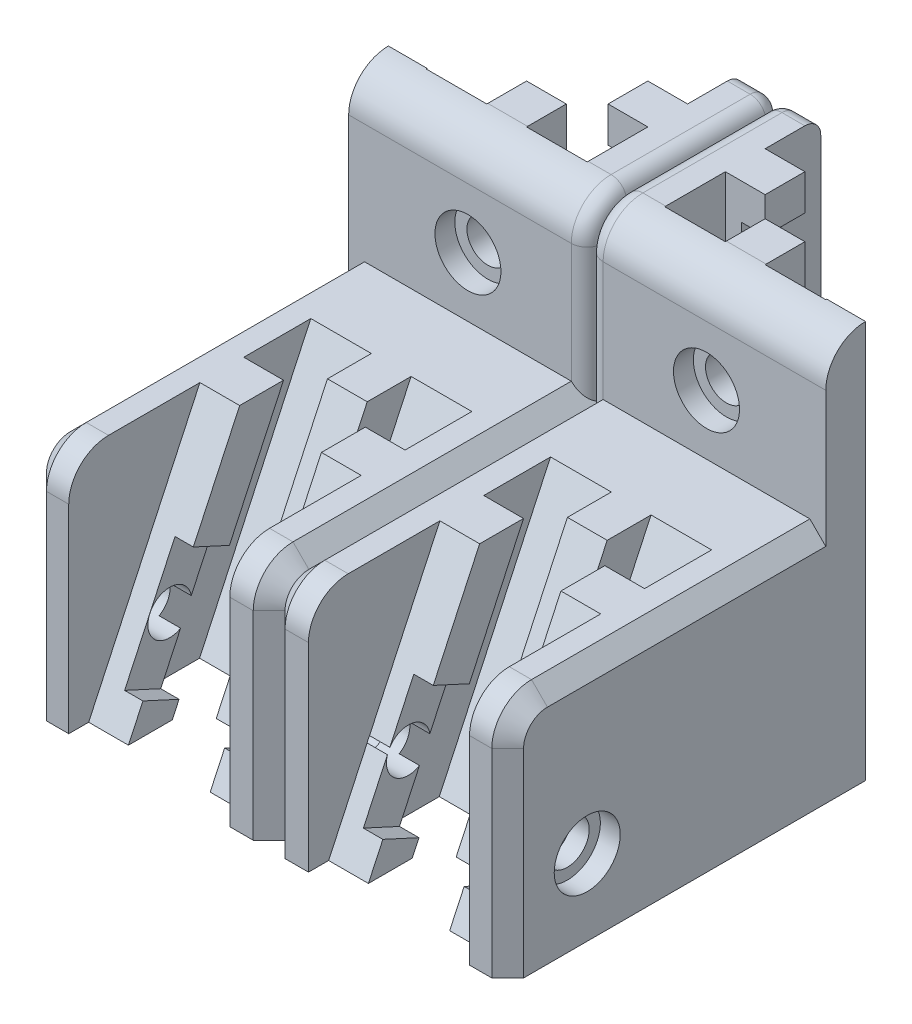
SolidWorks part; units mm, degrees
ref_plane "Front Plane" through (0, 0, 0) normal (0, 0, 1) x (1, 0, 0)
ref_plane "Top Plane" through (0, 0, 0) normal (0, 1, 0) x (1, 0, 0)
ref_plane "Right Plane" through (0, 0, 0) normal (1, 0, 0) x (0, 0, -1)
sketch "Z extrusion mount" plane through (0, 0, 0) normal (0, 1, 0) x (1, 0, 0)
  line L1 (-15, -15) -> (15, -15)
  line L2 (-15, -15) -> (-15, 15)
  line L3 (-15, 15) -> (15, 15)
  line L4 (15, -15) -> (15, 15)
  line L5 (-15, -15) -> (15, 15) construction
  line L6 (-15, 15) -> (15, -15) construction
  point P0 (0, 0)
  dimension "D1" = 30
  dimension "D2" = 30
extrude "Boss-Extrude1" add sketch "Z extrusion mount" along normal blind 50
sketch "Sketch2" plane through (0, 50, 0) normal (0, 1, 0) x (1, 0, 0)
  line L0 (0, 10.125) -> (0, -10.125) construction
  line L1 (-10.125, -10.125) -> (10.125, -10.125)
  line L2 (-10.125, -10.125) -> (-10.125, 10.125)
  line L3 (-10.125, 10.125) -> (10.125, 10.125)
  line L4 (10.125, -10.125) -> (10.125, 10.125)
  line L5 (-10.125, -10.125) -> (10.125, 10.125) construction
  line L6 (-10.125, 10.125) -> (10.125, -10.125) construction
  line L7 (-10.125, 0) -> (10.125, 0) construction
  line L8 (0, -10.125) -> (-2.5, -10.125)
  line L9 (-2.5, -10.125) -> (-2.5, -5.125)
  line L10 (-2.5, -5.125) -> (2.5, -5.125)
  line L11 (2.5, -5.125) -> (2.5, -10.125)
  line L12 (10.125, 2.5) -> (5.125, 2.5)
  line L13 (5.125, 2.5) -> (5.125, -2.5)
  line L14 (5.125, -2.5) -> (10.125, -2.5)
  point P0 (0, 0)
  dimension "D1" = 20.25
  dimension "D2" = 20.25
  dimension "D3" = 5
  dimension "D4" = 5
  dimension "D5" = 2.5
  dimension "D6" = 2.5
  dimension "D7" = 5
  dimension "D8" = 5
extrude "Cut-Extrude1" cut sketch "Sketch2" against normal blind 50 contours L10 L11 L1 L4 L3 L2 L9 region at (-0.5294, 50, -0.5294)
sketch "Sketch3" plane through (0, 50, 0) normal (0, 1, 0) x (1, 0, 0)
  line L0 (15, -15) -> (15, 15) construction
  line L1 (-15, 15) -> (15, 15)
  line L2 (-15, 15) -> (-15, 9.4943)
  line L3 (-15, 9.4943) -> (15, 9.4943)
  line L4 (15, 15) -> (15, 9.4943)
extrude "Cut-Extrude3" cut sketch "Sketch3" against normal blind 50
sketch "Sketch4" plane through (0, 0, 15) normal (0, 0, 1) x (1, 0, 0)
  line L0 (15, 50) -> (15, 0) construction
  line L1 (-15, 0) -> (15, 0)
  line L2 (-15, 0) -> (-15, 30)
  line L3 (-15, 30) -> (15, 30)
  line L4 (15, 0) -> (15, 30)
  line L5 (-15, 0) -> (15, 30) construction
  line L6 (-15, 30) -> (15, 0) construction
  point P0 (0, 15)
  dimension "D1" = 30
extrude "Boss-Extrude3" add sketch "Sketch4" along normal blind 40
sketch "Sketch11" plane through (-15, 0, 0) normal (-1, 0, 0) x (0, 0, 1)
  line L0 (35, 30) -> (55, -12.8901) construction
  line L1 (55, 30) -> (15, 30) construction
  line L2 (55, 30) -> (55, 0) construction
  line L3 (45, 8.5549) -> (45, 9.5549) construction
  circle A0 centre (45, 9.5549) radius 2.75
  dimension "D2" = 5.5
  dimension "D1" = 65
  dimension "D3" = 1
ref_plane "45 Angle Plane" through (-15, 30, 35) normal (0, 0.9063, -0.4226) x (-1, 0, 0)
sketch "Sketch12" plane through (-15, 30, 35) normal (0, 0.9063, -0.4226) x (-1, 0, 0)
  line L0 (-14.9267, 10.7882) -> (-14.9267, -9.4618) construction
  line L1 (-25.0517, -9.4618) -> (-4.8017, -9.4618)
  line L2 (-25.0517, -9.4618) -> (-25.0517, 10.7882)
  line L3 (-25.0517, 10.7882) -> (-4.8017, 10.7882)
  line L4 (-4.8017, -9.4618) -> (-4.8017, 10.7882)
  line L5 (-25.0517, -9.4618) -> (-4.8017, 10.7882) construction
  line L6 (-25.0517, 10.7882) -> (-4.8017, -9.4618) construction
  line L7 (-25.3, 0.6632) -> (-4.8017, 0.6632) construction
  line L8 (-14.9267, 10.7882) -> (-17.4408, 10.7882)
  line L9 (-17.4408, 10.7882) -> (-17.4408, 5.7882)
  line L10 (-17.4408, 5.7882) -> (-12.4408, 5.7882)
  line L11 (-12.4408, 5.7882) -> (-12.4408, 10.7882)
  line L12 (-14.9267, 11.0365) -> (-14.9267, -9.4618) construction
  line L13 (-4.8017, 3.1773) -> (-9.8017, 3.1773)
  line L14 (-9.8017, 3.1773) -> (-9.8017, -1.8227)
  line L15 (-9.8017, -1.8227) -> (-4.8017, -1.8227)
  line L16 (-4.5534, 0.6632) -> (-25.0517, 0.6632) construction
  line L17 (-12.4126, -9.4618) -> (-12.4126, -4.4618)
  line L18 (-12.4126, -4.4618) -> (-17.4126, -4.4618)
  line L19 (-17.4126, -4.4618) -> (-17.4126, -9.4618)
  line L20 (-14.9267, -9.7101) -> (-14.9267, 10.7882) construction
  line L21 (-25.0517, -1.851) -> (-20.0517, -1.851)
  line L22 (-20.0517, -1.851) -> (-20.0517, 3.149)
  line L23 (-20.0517, 3.149) -> (-25.0517, 3.149)
  point P0 (-14.9267, 0.6632)
  point P34 (-14.9267, 0.6632)
  dimension "D1" = 20.25
  dimension "D2" = 20.25
  dimension "D3" = 5
  dimension "D4" = 5
  dimension "D5" = 4
extrude "Cut-Extrude4" cut sketch "Sketch12" against normal through all and the other way blind 10 contours L23 L22 L21 L2 L1 L19 L18 L17 L4 L15 L14 L13 L3 L11 L10 L9 region at (-0.0733, 30.2803, 35.601)
fillet "Fillet1" radius 5 1 edges at (0, 30, 55)
fillet "Fillet2" radius 5 1 edges at (0, 50, 15)
extrude "Cut-Extrude14" cut sketch "Sketch11" against normal blind 30
sketch "Sketch22" plane through (15, 0, 0) normal (1, 0, 0) x (0, 0, -1)
  circle A0 centre (-45, 9.5549) radius 4.15
  dimension "D1" = 8.3
extrude "Cut-Extrude17" cut sketch "Sketch22" against normal blind 2.5
sketch "Sketch23" plane through (-15, 0, 0) normal (-1, 0, 0) x (0, 0, 1)
  circle A0 centre (45, 9.5549) radius 4.15
  dimension "D1" = 8.3
extrude "Cut-Extrude18" cut sketch "Sketch23" against normal blind 2.5
fillet "Fillet4" radius 2 3 edges at (15, 50, 0.2528) (15, 48.5355, 13.5355)
sketch "Sketch24" plane through (0, 50, 0) normal (0, 1, 0) x (1, 0, 0)
  line L2 (-15, -10) -> (-10.125, -10)
  line L3 (-15, -10) -> (-15, 9.4943)
  line L4 (-15, 9.4943) -> (-10.125, 9.4943)
  line L5 (-10.125, -10) -> (-10.125, 9.4943)
extrude "Cut-Extrude19" cut sketch "Sketch24" against normal through all
sketch "Sketch25" plane through (15, 0, 0) normal (1, 0, 0) x (0, 0, -1)
  line L0 (9.4943, 0) -> (9.4943, 48) construction
  line L1 (9.4943, 48) -> (-10, 48) construction
  line L2 (-55, 0) -> (9.4943, 0) construction
  circle A0 centre (-0.0057, 38) radius 2.625
  circle A1 centre (-0.0057, 10) radius 2.625
  dimension "D1" = 5.25
  dimension "D2" = 5.25
  dimension "D5" = 9.5
  dimension "D6" = 9.5
  dimension "D3" = 10
  dimension "D4" = 10
extrude "Cut-Extrude20" cut sketch "Sketch25" against normal through all
sketch "Sketch26" plane through (15, 0, 0) normal (1, 0, 0) x (0, 0, -1)
  circle A0 centre (-0.0057, 38) radius 4.15
  circle A1 centre (-0.0057, 10) radius 4.15
  dimension "D1" = 8.3
  dimension "D2" = 8.3
extrude "Cut-Extrude21" cut sketch "Sketch26" against normal blind 2.5
sketch "Sketch27" plane through (0, 0, 15) normal (0, 0, 1) x (1, 0, 0)
  line L0 (0, 45) -> (0, 37.5) construction
  line L1 (13, 45) -> (-15, 45) construction
  circle A0 centre (0, 37.5) radius 2.625
  dimension "D2" = 5.25
  dimension "D1" = 7.5
extrude "Cut-Extrude23" cut sketch "Sketch27" against normal through all
sketch "Sketch28" plane through (0, 0, 15) normal (0, 0, 1) x (1, 0, 0)
  circle A0 centre (0, 37.5) radius 4.15
  dimension "D1" = 8.3
extrude "Cut-Extrude24" cut sketch "Sketch28" against normal blind 2.5
sketch "Sketch29" plane through (0, 0, 5.125) normal (0, 0, -1) x (-1, 0, 0)
  line L1 (-5, 30) -> (5, 30)
  line L2 (-5, 30) -> (-5, 45)
  line L3 (-5, 45) -> (5, 45)
  line L4 (5, 30) -> (5, 45)
  line L5 (-5, 30) -> (5, 45) construction
  line L6 (-5, 45) -> (5, 30) construction
  point P0 (0, 37.5)
  dimension "D1" = 10
  dimension "D2" = 15
extrude "Cut-Extrude25" cut sketch "Sketch29" against normal blind 3
sketch "Sketch31" plane through (5.125, 0, 0) normal (-1, 0, 0) x (0, 0, 1)
  line L1 (-4.9943, 30.5) -> (5.0057, 30.5)
  line L2 (-4.9943, 30.5) -> (-4.9943, 45.5)
  line L3 (-4.9943, 45.5) -> (5.0057, 45.5)
  line L4 (5.0057, 30.5) -> (5.0057, 45.5)
  line L5 (-4.9943, 30.5) -> (5.0057, 45.5) construction
  line L6 (-4.9943, 45.5) -> (5.0057, 30.5) construction
  line L7 (-4.9943, 2.5) -> (5.0057, 2.5)
  line L8 (-4.9943, 2.5) -> (-4.9943, 17.5)
  line L9 (-4.9943, 17.5) -> (5.0057, 17.5)
  line L10 (5.0057, 2.5) -> (5.0057, 17.5)
  line L11 (-4.9943, 2.5) -> (5.0057, 17.5) construction
  line L12 (-4.9943, 17.5) -> (5.0057, 2.5) construction
  point P0 (0.0057, 38)
  point P6 (0.0057, 10)
  dimension "D1" = 15
  dimension "D2" = 10
  dimension "D3" = 15
  dimension "D4" = 10
extrude "Cut-Extrude27" cut sketch "Sketch31" against normal blind 3
sketch "Sketch33" plane through (-15, 30, 35) normal (0, 0.9063, -0.4226) x (-1, 0, 0)
  line L0 (0, 16.4815) -> (-30, 16.4815) construction
  line L1 (-25.0517, 16.4815) -> (-4.8017, 16.4815)
  line L2 (-25.0517, 16.4815) -> (-25.0517, 5.6981)
  line L3 (-25.0517, 5.6981) -> (-4.8017, 5.6981)
  line L4 (-4.8017, 16.4815) -> (-4.8017, 5.6981)
  line L5 (-4.8017, 3.1773) -> (-4.8017, 10.7882) construction
extrude "Cut-Extrude29" cut sketch "Sketch33" against normal through all
sketch "Sketch35" plane through (0, 0, 0) normal (1, 0, 0) x (0, 0, -1)
  line L0 (-45, 9.5549) -> (-35.3755, 30.4885) construction
  line L1 (-37.7474, 14.4752) -> (-45.0337, 17.8251)
  line L2 (-37.7474, 14.4752) -> (-44.9663, 1.2847)
  line L3 (-45.0337, 17.8251) -> (-52.2526, 4.6347)
  line L4 (-44.9663, 1.2847) -> (-52.2526, 4.6347)
  dimension "D1" = 15
  dimension "D2" = 7.5
  dimension "D3" = 8
  dimension "D4" = 4
extrude "Cut-Extrude30" cut sketch "Sketch35" against normal mid plane 15
chamfer "Chamfer1" distance 2 angle 45 6 edges at (15, 12.5, 55) (15, 28.5355, 53.5355) (-15, 12.5, 55) (-15, 28.5355, 53.5355)
fillet "Fillet5" radius 2 3 edges at (11.5625, 50, -9.4943) (14.4142, 49.4142, -9.4943) (15, 24, -9.4943)
mirror "Mirror1" about plane through (15, 50, 15) normal (-1, 0, 0) of bodies 139
